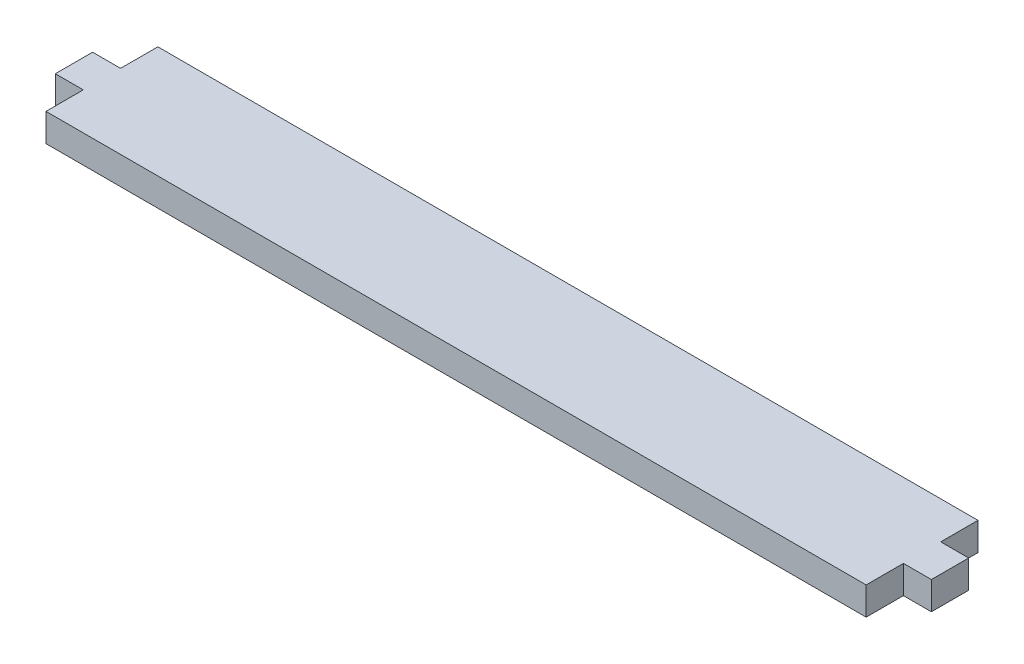
SolidWorks part; units mm, degrees
ref_plane "Front Plane" through (0, 0, 0) normal (0, 0, 1) x (1, 0, 0)
ref_plane "Top Plane" through (0, 0, 0) normal (0, 1, 0) x (1, 0, 0)
ref_plane "Right Plane" through (0, 0, 0) normal (1, 0, 0) x (0, 0, -1)
sketch "Sketch1" plane through (0, 0, 0) normal (0, 1, 0) x (1, 0, 0)
  line L1 (139.7, -19.05) -> (-139.7, -19.05)
  line L2 (139.7, -19.05) -> (139.7, 19.05)
  line L3 (139.7, 19.05) -> (-139.7, 19.05)
  line L4 (-139.7, -19.05) -> (-139.7, 19.05)
  line L5 (139.7, -19.05) -> (-139.7, 19.05) construction
  line L6 (139.7, 19.05) -> (-139.7, -19.05) construction
  point P0 (0, 0)
  dimension "D1" = 279.4
  dimension "D2" = 38.1
extrude "Boss-Extrude1" add sketch "Sketch1" along normal blind 9.525
sketch "Sketch2" plane through (139.7, 0, 0) normal (1, 0, 0) x (0, 0, -1)
  line L0 (-19.05, 0) -> (19.05, 0) construction
  line L1 (-6.35, 0) -> (6.35, 0)
  line L2 (-6.35, 0) -> (-6.35, 9.525)
  line L3 (-6.35, 9.525) -> (6.35, 9.525)
  line L4 (6.35, 0) -> (6.35, 9.525)
  line L5 (-19.05, 9.525) -> (19.05, 9.525) construction
  line L6 (-19.05, 9.525) -> (-19.05, 0) construction
  dimension "D1" = 12.7
  dimension "D2" = 12.7
extrude "Boss-Extrude2" add sketch "Sketch2" along normal blind 9.525
mirror "Mirror1" about plane through (0, 0, 0) normal (1, 0, 0) of "Boss-Extrude2"
